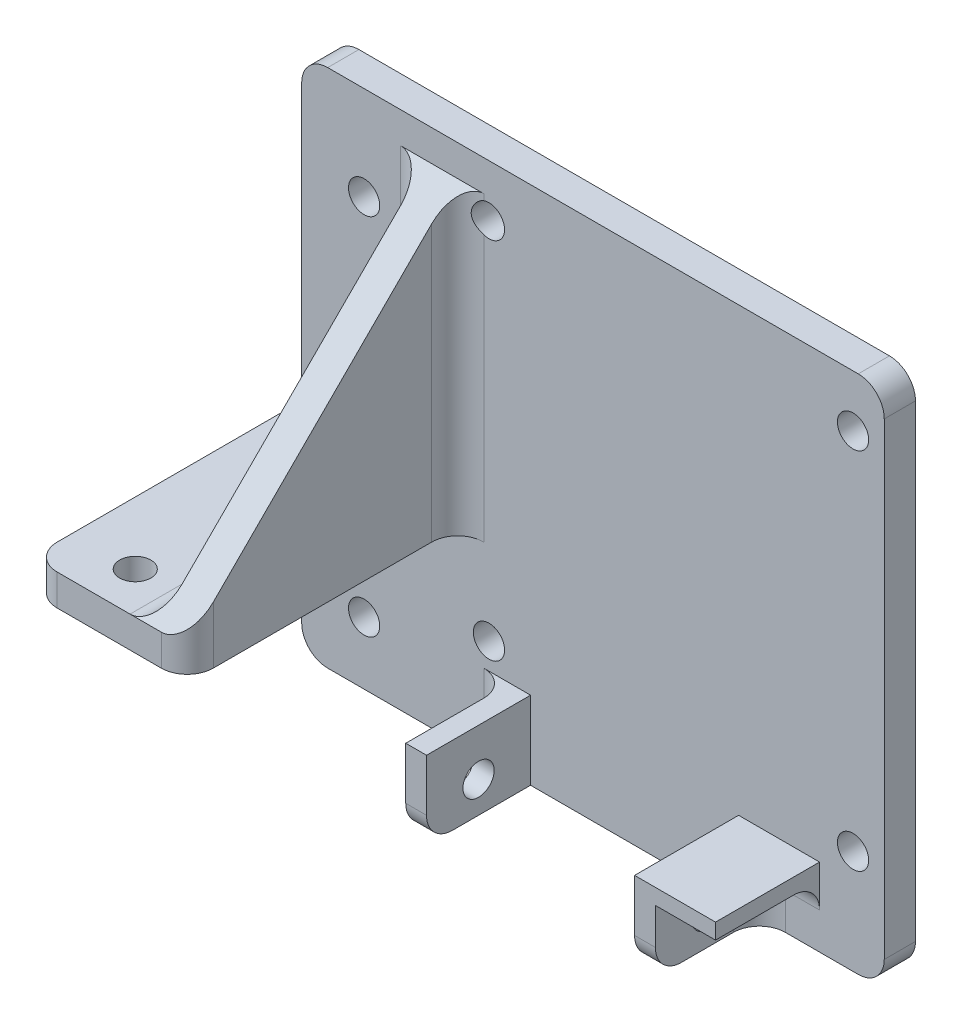
SolidWorks part; units mm, degrees
ref_plane "Front Plane" through (0, 0, 0) normal (0, 0, 1) x (1, 0, 0)
ref_plane "Top Plane" through (0, 0, 0) normal (0, 1, 0) x (1, 0, 0)
ref_plane "Right Plane" through (0, 0, 0) normal (1, 0, 0) x (0, 0, -1)
sketch "Sketch1" plane through (0, 0, 0) normal (0, 0, 1) x (1, 0, 0)
  line L1 (0, 0) -> (56, 0)
  line L2 (0, 0) -> (0, 50)
  line L3 (0, 50) -> (56, 50)
  line L4 (56, 0) -> (56, 50)
  dimension "D1" = 56
  dimension "D2" = 50
extrude "Boss-Extrude1" add sketch "Sketch1" along normal blind 3
sketch "Sketch2" plane through (0, 0, 3) normal (0, 0, 1) x (1, 0, 0)
  line L0 (6, -4.5714) -> (6, 59.5728) construction
  line L1 (18, 10) -> (53, 10) construction
  line L2 (18, 10) -> (18, 45) construction
  line L3 (18, 45) -> (53, 45) construction
  line L4 (53, 10) -> (53, 45) construction
  circle A3 centre (18, 10) radius 1.5
  circle A4 centre (18, 45) radius 1.5
  circle A5 centre (53, 45) radius 1.5
  circle A6 centre (53, 10) radius 1.5
  circle A7 centre (6, 6) radius 1.5
  circle A8 centre (6, 41) radius 1.5
  dimension "D1" = 3
  dimension "D8" = 3
  dimension "D2" = 35
  dimension "D3" = 35
  dimension "D4" = 12
  dimension "D5" = 10
  dimension "D6" = 35
  dimension "D7" = 6
  dimension "D9" = 6
extrude "Cut-Extrude1" cut sketch "Sketch2" against normal through all
sketch "Sketch3" plane through (0, 0, 3) normal (0, 0, 1) x (1, 0, 0)
  line L0 (0, 50) -> (0, 0) construction
  line L1 (0, 18) -> (12, 18)
  line L2 (0, 18) -> (0, 21)
  line L3 (0, 21) -> (12, 21)
  line L4 (12, 18) -> (12, 21)
  dimension "D1" = 3
  dimension "D2" = 12
  dimension "D3" = 18
extrude "Boss-Extrude2" add sketch "Sketch3" along normal blind 26
sketch "Sketch5" plane through (0, 21, 0) normal (0, 1, 0) x (1, 0, 0)
  line L0 (6, -29.5175) -> (6, 3.8156) construction
  line L1 (0, -29) -> (0, -3) construction
  line L5 (56, -3) -> (0, -3) construction
  circle A0 centre (6, -7) radius 1.5
  circle A1 centre (6, -25) radius 1.5
  dimension "D2" = 3
  dimension "D1" = 6
  dimension "D3" = 18
  dimension "D4" = 4
extrude "Cut-Extrude2" cut sketch "Sketch5" against normal blind 10
sketch "Sketch6" plane through (12, 0, 0) normal (1, 0, 0) x (0, 0, -1)
  line L0 (-3, 18) -> (-29, 18)
  line L1 (-29, 18) -> (-29, 21)
  line L2 (-29, 21) -> (-3, 47)
  line L3 (-3, 47) -> (-3, 18)
  line L4 (-29, 21) -> (-3, 21) construction
  dimension "D1" = 45
extrude "Boss-Extrude3" add sketch "Sketch6" along normal blind 3
sketch "Sketch7" plane through (0, 0, 3) normal (0, 0, 1) x (1, 0, 0)
  line L0 (0, 0) -> (56, 0) construction
  line L1 (20, 0) -> (22, 0)
  line L2 (20, 0) -> (20, 7.5)
  line L4 (22, 0) -> (22, 7.5)
  line L6 (43.9994, 0) -> (42, 0)
  line L7 (43.9994, 0) -> (43.9994, 6)
  line L10 (42, 7.5) -> (49.7818, 7.5)
  line L11 (49.7818, 7.5) -> (49.7818, 6)
  line L12 (49.7818, 6) -> (43.9994, 6)
  line L13 (20, 7.5) -> (22, 7.5)
  line L14 (42, 7.5) -> (42, 0)
  dimension "D1" = 7.5
  dimension "D2" = 7.5
  dimension "D3" = 20
  dimension "D4" = 2
  dimension "D6" = 1.5
extrude "Boss-Extrude4" add sketch "Sketch7" along normal blind 10
sketch "Sketch8" plane through (20, 0, 0) normal (-1, 0, 0) x (0, 0, 1)
  line L0 (3, 3) -> (13, 3) construction
  line L3 (13, 0) -> (3, 0) construction
  line L6 (13, 7.5) -> (13, 0) construction
  circle A0 centre (8, 3) radius 1.5
  dimension "D1" = 3
  dimension "D2" = 3
  dimension "D3" = 5
extrude "Cut-Extrude3" cut sketch "Sketch8" against normal through all
fillet "Fillet1" radius 2.5 4 edges at (0, 50, 1.5) (0, 0, 1.5) (56, 0, 1.5) (56, 50, 1.5)
fillet "Fillet2" radius 2.5 6 edges at (20, 3.75, 3) (12, 21, 16) (12, 34, 3) (15, 32.5, 3) (46.8906, 6, 3) (43.9994, 3, 3)
fillet "Fillet3" radius 2.5 2 edges at (0, 19.5, 29) (15, 19.5, 29)
fillet "Fillet4" radius 2.5 2 edges at (42.9997, 0, 13) (21, 0, 13)
